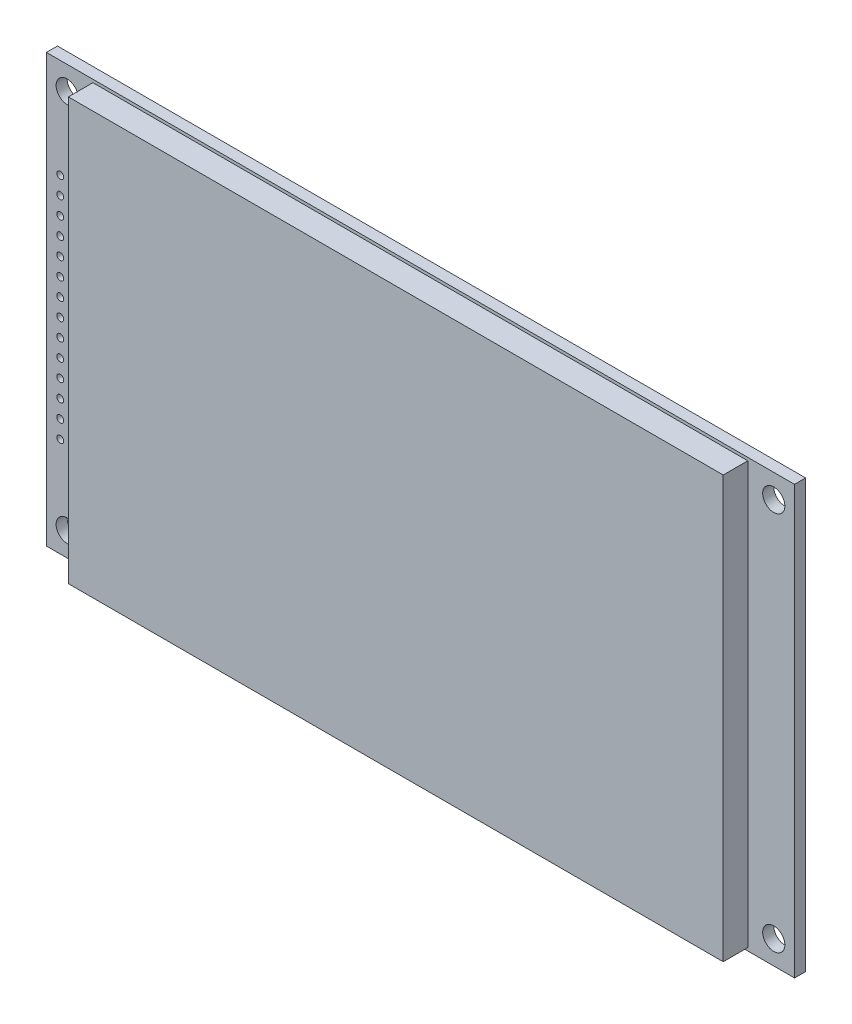
SolidWorks part; units mm, degrees
ref_plane "Front Plane" through (0, 0, 0) normal (0, 0, 1) x (1, 0, 0)
ref_plane "Top Plane" through (0, 0, 0) normal (0, 1, 0) x (1, 0, 0)
ref_plane "Right Plane" through (0, 0, 0) normal (1, 0, 0) x (0, 0, -1)
sketch "Sketch1" plane through (0, 0, 0) normal (0, 0, 1) x (1, 0, 0)
  line L1 (-54.02, 30.87) -> (54.02, 30.87)
  line L2 (-54.02, 30.87) -> (-54.02, -30.87)
  line L3 (-54.02, -30.87) -> (54.02, -30.87)
  line L4 (54.02, 30.87) -> (54.02, -30.87)
  line L5 (-54.02, 30.87) -> (54.02, -30.87) construction
  line L6 (-54.02, -30.87) -> (54.02, 30.87) construction
  circle A0 centre (-51.02, 27.45) radius 1.6
  circle A1 centre (-51.02, -27.45) radius 1.6
  circle A2 centre (51.02, -27.45) radius 1.6
  circle A3 centre (51.02, 27.45) radius 1.6
  point P0 (0, 0)
  dimension "D5" = 3.2
  dimension "D6" = 3.2
  dimension "D9" = 3.2
  dimension "D1" = 61.74
  dimension "D2" = 108.04
  dimension "D3" = 3.42
  dimension "D4" = 3
  dimension "D7" = 3
  dimension "D8" = 3.42
  dimension "D10" = 3
  dimension "D11" = 3.42
  dimension "D12" = 3
  dimension "D13" = 3.42
extrude "Boss-Extrude1" add sketch "Sketch1" along normal blind 1.6
sketch "Sketch2" plane through (0, 0, 1.6) normal (0, 0, 1) x (1, 0, 0)
  line L0 (-47.3, 0) -> (47.27, 0) construction
  line L1 (47.27, 30.44) -> (-47.3, 30.44)
  line L2 (47.27, 30.44) -> (47.27, -30.44)
  line L3 (47.27, -30.44) -> (-47.3, -30.44)
  line L4 (-47.3, 30.44) -> (-47.3, -30.44)
  line L5 (-54.02, 30.87) -> (-54.02, -30.87) construction
  dimension "D1" = 94.57
  dimension "D2" = 60.88
  dimension "D3" = 6.75
  dimension "D4" = 6.72
extrude "Boss-Extrude2" add sketch "Sketch2" along normal blind 3.55
sketch "Sketch3" plane through (0, 0, 1.6) normal (0, 0, 1) x (1, 0, 0)
  line L0 (54.02, 30.87) -> (-54.02, 30.87) construction
  circle A0 centre (-52.02, 16.51) radius 0.5
  circle A1 centre (-52.02, 13.97) radius 0.5
  circle A2 centre (-52.02, 11.43) radius 0.5
  circle A3 centre (-52.02, 8.89) radius 0.5
  circle A4 centre (-52.02, 6.35) radius 0.5
  circle A5 centre (-52.02, 3.81) radius 0.5
  circle A6 centre (-52.02, 1.27) radius 0.5
  circle A7 centre (-52.02, -1.27) radius 0.5
  circle A8 centre (-52.02, -3.81) radius 0.5
  circle A9 centre (-52.02, -6.35) radius 0.5
  circle A10 centre (-52.02, -8.89) radius 0.5
  circle A11 centre (-52.02, -11.43) radius 0.5
  circle A12 centre (-52.02, -13.97) radius 0.5
  circle A13 centre (-52.02, -16.51) radius 0.5
  dimension "D3" = 1
  dimension "D1" = 14.36
  dimension "D2" = 2
  dimension "D4" = 14
extrude "Cut-Extrude1" cut sketch "Sketch3" against normal blind 3.55
sketch "Sketch4" plane through (0, 0, 0) normal (0, 0, -1) x (-1, 0, 0)
  line L4 (-54.02, 30.87) -> (-54.02, -30.87)
  line L5 (-54.02, -30.87) -> (54.02, -30.87)
  line L6 (54.02, -30.87) -> (54.02, 30.87)
  line L7 (54.02, 30.87) -> (-54.02, 30.87)
  line L8 (-54.02, 30.87) -> (-54.02, -30.87)
  line L9 (-54.02, -30.87) -> (54.02, -30.87)
  line L10 (54.02, -30.87) -> (54.02, 30.87)
  line L11 (54.02, 30.87) -> (-54.02, 30.87)
  line L13 (51.02, 17.51) -> (53.02, 17.51)
  line L14 (51.02, 17.51) -> (51.02, -17.51)
  line L15 (51.02, -17.51) -> (53.02, -17.51)
  line L16 (53.02, 17.51) -> (53.02, -17.51)
  circle A0 centre (52.02, -16.51) radius 0.5 construction
  circle A1 centre (52.02, -16.51) radius 0.5
  circle A2 centre (52.02, 16.51) radius 0.5 construction
  circle A3 centre (52.02, 16.51) radius 0.5
  circle M9 centre (52.02, 16.51) radius 0.5
  circle M10 centre (52.02, 13.97) radius 0.5
  circle M11 centre (52.02, 11.43) radius 0.5
  circle M12 centre (52.02, 8.89) radius 0.5
  circle M13 centre (52.02, 6.35) radius 0.5
  circle M14 centre (52.02, 3.81) radius 0.5
  circle M15 centre (52.02, 1.27) radius 0.5
  circle M16 centre (52.02, -1.27) radius 0.5
  circle M17 centre (52.02, -3.81) radius 0.5
  circle M18 centre (52.02, -6.35) radius 0.5
  circle M19 centre (52.02, -8.89) radius 0.5
  circle M20 centre (52.02, -11.43) radius 0.5
  circle M21 centre (52.02, -13.97) radius 0.5
  circle M22 centre (52.02, -16.51) radius 0.5
  dimension "D2" = 1
  dimension "D3" = 1
  dimension "D4" = 1
  dimension "D5" = 1
  dimension "D1" = 0
extrude "Boss-Extrude3" add sketch "Sketch4" along normal blind 2.5 contours L16 L13 L14 L15 M10 M12 M14 M16 M18 M20 M22 M21 M19 M17 M15 M13 M11 M9 region at (-52.02, 0, 0)
sketch "Sketch5" plane through (0, 0, -2.5) normal (0, 0, -1) x (-1, 0, 0)
  circle A0 centre (52.02, -16.51) radius 0.5 construction
  circle A1 centre (52.02, -13.97) radius 0.5 construction
  circle A2 centre (52.02, -11.43) radius 0.5 construction
  circle A3 centre (52.02, -8.89) radius 0.5 construction
  circle A4 centre (52.02, -6.35) radius 0.5 construction
  circle A5 centre (52.02, -3.81) radius 0.5 construction
  circle A6 centre (52.02, -1.27) radius 0.5 construction
  circle A7 centre (52.02, 1.27) radius 0.5 construction
  circle A8 centre (52.02, 3.81) radius 0.5 construction
  circle A9 centre (52.02, 6.35) radius 0.5 construction
  circle A10 centre (52.02, 8.89) radius 0.5 construction
  circle A11 centre (52.02, 11.43) radius 0.5 construction
  circle A12 centre (52.02, 13.97) radius 0.5 construction
  circle A13 centre (52.02, 16.51) radius 0.5 construction
  circle A14 centre (52.02, -16.51) radius 0.5
  circle A15 centre (52.02, -13.97) radius 0.5
  circle A16 centre (52.02, -11.43) radius 0.5
  circle A17 centre (52.02, -8.89) radius 0.5
  circle A18 centre (52.02, -6.35) radius 0.5
  circle A19 centre (52.02, -3.81) radius 0.5
  circle A20 centre (52.02, -1.27) radius 0.5
  circle A21 centre (52.02, 1.27) radius 0.5
  circle A22 centre (52.02, 3.81) radius 0.5
  circle A23 centre (52.02, 6.35) radius 0.5
  circle A24 centre (52.02, 8.89) radius 0.5
  circle A25 centre (52.02, 11.43) radius 0.5
  circle A26 centre (52.02, 13.97) radius 0.5
  circle A27 centre (52.02, 16.51) radius 0.5
extrude "Boss-Extrude4" add sketch "Sketch5" along normal blind 5.84 separate body
